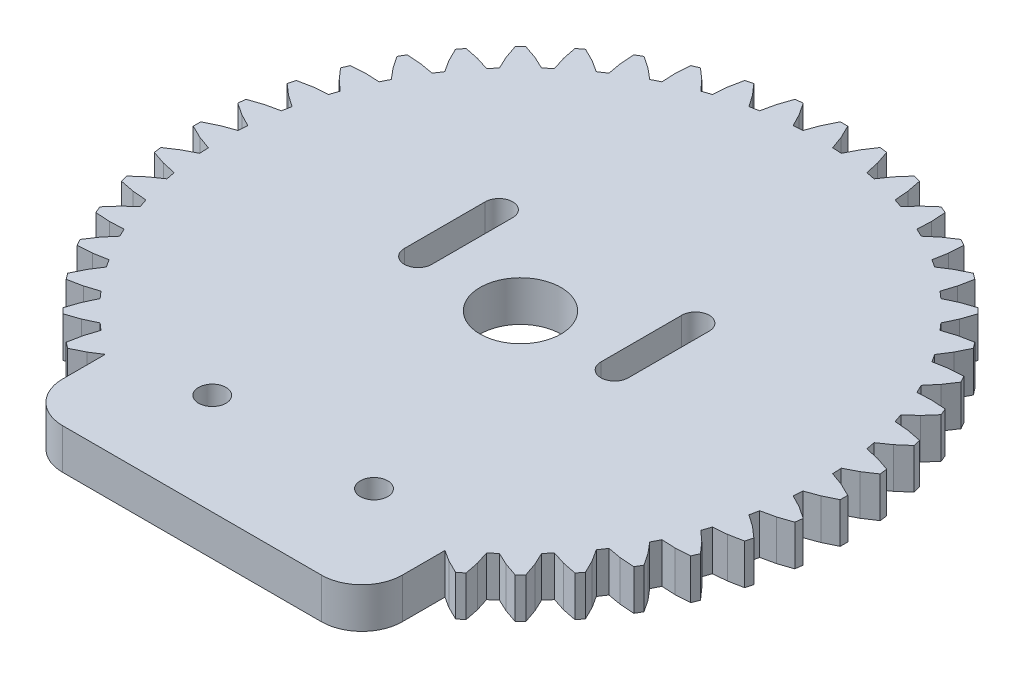
SolidWorks part; units mm, degrees
material "Acrylic (Medium-high impact)"
ref_plane "Front Plane" through (0, 0, 0) normal (0, 0, 1) x (1, 0, 0)
ref_plane "Top Plane" through (0, 0, 0) normal (0, 1, 0) x (1, 0, 0)
ref_plane "Right Plane" through (0, 0, 0) normal (1, 0, 0) x (0, 0, -1)
sketch "Sketch2" plane through (0, 0, 0) normal (0, 1, 0) x (1, 0, 0)
  line L0 (83.8835, 67.191) -> (85.5092, 66.6061)
  line L1 (85.5092, 66.6061) -> (87.1271, 65.8138)
  line L2 (87.1271, 65.8138) -> (87.1271, 64.8854)
  line L3 (87.1271, 64.8854) -> (85.5092, 64.0931)
  line L4 (85.5092, 64.0931) -> (83.8835, 63.5083)
  line L5 (83.8835, 63.5083) -> (83.8095, 62.3776)
  line L6 (83.8095, 62.3776) -> (85.3448, 61.5855)
  line L7 (85.3448, 61.5855) -> (86.8456, 60.5888)
  line L8 (86.8456, 60.5888) -> (86.7243, 59.6683)
  line L9 (86.7243, 59.6683) -> (85.0168, 59.094)
  line L10 (85.0168, 59.094) -> (83.3288, 58.7263)
  line L11 (83.3288, 58.7263) -> (83.1077, 57.615)
  line L12 (83.1077, 57.615) -> (84.5266, 56.6293)
  line L13 (84.5266, 56.6293) -> (85.8844, 55.4453)
  line L14 (85.8844, 55.4453) -> (85.6441, 54.5485)
  line L15 (85.6441, 54.5485) -> (83.8761, 54.202)
  line L16 (83.8761, 54.202) -> (82.1545, 54.0577)
  line L17 (82.1545, 54.0577) -> (81.7903, 52.9848)
  line L18 (81.7903, 52.9848) -> (83.0684, 51.8222)
  line L19 (83.0684, 51.8222) -> (84.26, 50.4711)
  line L20 (84.26, 50.4711) -> (83.9048, 49.6134)
  line L21 (83.9048, 49.6134) -> (82.1066, 49.5006)
  line L22 (82.1066, 49.5006) -> (80.3809, 49.5823)
  line L23 (80.3809, 49.5823) -> (79.8799, 48.5661)
  line L24 (79.8799, 48.5661) -> (80.9952, 47.2468)
  line L25 (80.9952, 47.2468) -> (82.0003, 45.7516)
  line L26 (82.0003, 45.7516) -> (81.5361, 44.9476)
  line L27 (81.5361, 44.9476) -> (79.7387, 45.0704)
  line L28 (79.7387, 45.0704) -> (78.0384, 45.3766)
  line L29 (78.0384, 45.3766) -> (77.4089, 44.4346)
  line L30 (77.4089, 44.4346) -> (78.3426, 42.9809)
  line L31 (78.3426, 42.9809) -> (79.1439, 41.3674)
  line L32 (79.1439, 41.3674) -> (78.5788, 40.6309)
  line L33 (78.5788, 40.6309) -> (76.8128, 40.9873)
  line L34 (76.8128, 40.9873) -> (75.167, 41.5128)
  line L35 (75.167, 41.5128) -> (74.4199, 40.6609)
  line L36 (74.4199, 40.6609) -> (75.1558, 39.0979)
  line L37 (75.1558, 39.0979) -> (75.7397, 37.3936)
  line L38 (75.7397, 37.3936) -> (75.0832, 36.737)
  line L39 (75.0832, 36.737) -> (73.3788, 37.3209)
  line L40 (73.3788, 37.3209) -> (71.8158, 38.0569)
  line L41 (71.8158, 38.0569) -> (70.9639, 37.3097)
  line L42 (70.9639, 37.3097) -> (71.4895, 35.6639)
  line L43 (71.4895, 35.6639) -> (71.8459, 33.898)
  line L44 (71.8459, 33.898) -> (71.1093, 33.3328)
  line L45 (71.1093, 33.3328) -> (69.4958, 34.1341)
  line L46 (69.4958, 34.1341) -> (68.0421, 35.0679)
  line L47 (68.0421, 35.0679) -> (67.1001, 34.4384)
  line L48 (67.1001, 34.4384) -> (67.4064, 32.738)
  line L49 (67.4064, 32.738) -> (67.5292, 30.9407)
  line L50 (67.5292, 30.9407) -> (66.7251, 30.4764)
  line L51 (66.7251, 30.4764) -> (65.23, 31.4815)
  line L52 (65.23, 31.4815) -> (63.9107, 32.5969)
  line L53 (63.9107, 32.5969) -> (62.8945, 32.0958)
  line L54 (62.8945, 32.0958) -> (62.9762, 30.3701)
  line L55 (62.9762, 30.3701) -> (62.8633, 28.572)
  line L56 (62.8633, 28.572) -> (62.0056, 28.2167)
  line L57 (62.0056, 28.2167) -> (60.6545, 29.4083)
  line L58 (60.6545, 29.4083) -> (59.4919, 30.6864)
  line L59 (59.4919, 30.6864) -> (58.419, 30.3222)
  line L60 (58.419, 30.3222) -> (58.2748, 28.6006)
  line L61 (58.2748, 28.6006) -> (57.9283, 26.8327)
  line L62 (57.9283, 26.8327) -> (57.0315, 26.5924)
  line L63 (57.0315, 26.5924) -> (55.8474, 27.9502)
  line L64 (55.8474, 27.9502) -> (54.8618, 29.369)
  line L65 (54.8618, 29.369) -> (53.7504, 29.1479)
  line L66 (53.7504, 29.1479) -> (53.3827, 27.4599)
  line L67 (53.3827, 27.4599) -> (52.8084, 25.7524)
  line L68 (52.8084, 25.7524) -> (51.888, 25.6311)
  line L69 (51.888, 25.6311) -> (50.8913, 27.1319)
  line L70 (50.8913, 27.1319) -> (50.0992, 28.6672)
  line L71 (50.0992, 28.6672) -> (48.9685, 28.5932)
  line L72 (48.9685, 28.5932) -> (48.3836, 26.9675)
  line L73 (48.3836, 26.9675) -> (47.5914, 25.3496)
  line L74 (47.5914, 25.3496) -> (46.6629, 25.3496)
  line L75 (46.6629, 25.3496) -> (45.8707, 26.9675)
  line L76 (45.8707, 26.9675) -> (45.2858, 28.5932)
  line L77 (45.2858, 28.5932) -> (44.1551, 28.6672)
  line L78 (44.1551, 28.6672) -> (43.363, 27.1319)
  line L79 (43.363, 27.1319) -> (42.3663, 25.6311)
  line L80 (42.3663, 25.6311) -> (41.4459, 25.7524)
  line L81 (41.4459, 25.7524) -> (40.8715, 27.4599)
  line L82 (40.8715, 27.4599) -> (40.5038, 29.1479)
  line L83 (40.5038, 29.1479) -> (39.3925, 29.369)
  line L84 (39.3925, 29.369) -> (38.4068, 27.9502)
  line L85 (38.4068, 27.9502) -> (37.2228, 26.5924)
  line L86 (37.2228, 26.5924) -> (36.326, 26.8327)
  line L87 (36.326, 26.8327) -> (35.9795, 28.6006)
  line L88 (35.9795, 28.6006) -> (35.8352, 30.3222)
  line L89 (35.8352, 30.3222) -> (34.7624, 30.6864)
  line L90 (34.7624, 30.6864) -> (33.5998, 29.4083)
  line L91 (33.5998, 29.4083) -> (32.2487, 28.2167)
  line L92 (32.2487, 28.2167) -> (31.3909, 28.572)
  line L93 (31.3909, 28.572) -> (31.2781, 30.3701)
  line L94 (31.2781, 30.3701) -> (31.3598, 32.0958)
  line L95 (31.3598, 32.0958) -> (30.3436, 32.5969)
  line L96 (30.3436, 32.5969) -> (29.0243, 31.4815)
  line L97 (29.0243, 31.4815) -> (27.5292, 30.4764)
  line L98 (27.5292, 30.4764) -> (26.7251, 30.9407)
  line L99 (26.7251, 30.9407) -> (26.8479, 32.738)
  line L100 (26.8479, 32.738) -> (27.1541, 34.4384)
  line L101 (27.1541, 34.4384) -> (26.2121, 35.0679)
  line L102 (26.2121, 35.0679) -> (24.7585, 34.1341)
  line L103 (24.7585, 34.1341) -> (23.1449, 33.3328)
  line L104 (23.1449, 33.3328) -> (22.4084, 33.898)
  line L105 (22.4084, 33.898) -> (22.7648, 35.6639)
  line L106 (22.7648, 35.6639) -> (23.2904, 37.3097)
  line L107 (23.2904, 37.3097) -> (22.4384, 38.0569)
  line L108 (22.4384, 38.0569) -> (20.8754, 37.3209)
  line L109 (20.8754, 37.3209) -> (19.1711, 36.737)
  line L110 (19.1711, 36.737) -> (18.5146, 37.3936)
  line L111 (18.5146, 37.3936) -> (19.0984, 39.0979)
  line L112 (19.0984, 39.0979) -> (19.8344, 40.6609)
  line L113 (19.8344, 40.6609) -> (19.0872, 41.5128)
  line L114 (19.0872, 41.5128) -> (17.4414, 40.9873)
  line L115 (17.4414, 40.9873) -> (15.6755, 40.6309)
  line L116 (15.6755, 40.6309) -> (15.1103, 41.3674)
  line L117 (15.1103, 41.3674) -> (15.9116, 42.9809)
  line L118 (15.9116, 42.9809) -> (16.8454, 44.4346)
  line L119 (16.8454, 44.4346) -> (16.2159, 45.3766)
  line L120 (16.2159, 45.3766) -> (14.5155, 45.0704)
  line L121 (14.5155, 45.0704) -> (12.7182, 44.9476)
  line L122 (12.7182, 44.9476) -> (12.2539, 45.7516)
  line L123 (12.2539, 45.7516) -> (13.2591, 47.2468)
  line L124 (13.2591, 47.2468) -> (14.3744, 48.5661)
  line L125 (14.3744, 48.5661) -> (13.8733, 49.5823)
  line L126 (13.8733, 49.5823) -> (12.1476, 49.5006)
  line L127 (12.1476, 49.5006) -> (10.3495, 49.6134)
  line L128 (10.3495, 49.6134) -> (9.9942, 50.4711)
  line L129 (9.9942, 50.4711) -> (11.1858, 51.8222)
  line L130 (11.1858, 51.8222) -> (12.4639, 52.9848)
  line L131 (12.4639, 52.9848) -> (12.0997, 54.0577)
  line L132 (12.0997, 54.0577) -> (10.3781, 54.202)
  line L133 (10.3781, 54.202) -> (8.6102, 54.5485)
  line L134 (8.6102, 54.5485) -> (8.3699, 55.4453)
  line L135 (8.3699, 55.4453) -> (9.7277, 56.6293)
  line L136 (9.7277, 56.6293) -> (11.1465, 57.615)
  line L137 (11.1465, 57.615) -> (10.9255, 58.7263)
  line L138 (10.9255, 58.7263) -> (9.2374, 59.094)
  line L139 (9.2374, 59.094) -> (7.5299, 59.6683)
  line L140 (7.5299, 59.6683) -> (7.4086, 60.5888)
  line L141 (7.4086, 60.5888) -> (8.9094, 61.5855)
  line L142 (8.9094, 61.5855) -> (10.4448, 62.3776)
  line L143 (10.4448, 62.3776) -> (10.3707, 63.5083)
  line L144 (10.3707, 63.5083) -> (8.745, 64.0931)
  line L145 (8.745, 64.0931) -> (7.1271, 64.8854)
  line L146 (7.1271, 64.8854) -> (7.1271, 65.8138)
  line L147 (7.1271, 65.8138) -> (8.745, 66.6061)
  line L148 (8.745, 66.6061) -> (10.3707, 67.191)
  line L149 (10.3707, 67.191) -> (10.4448, 68.3216)
  line L150 (10.4448, 68.3216) -> (8.9094, 69.1138)
  line L151 (8.9094, 69.1138) -> (7.4086, 70.1105)
  line L152 (7.4086, 70.1105) -> (7.5299, 71.0309)
  line L153 (7.5299, 71.0309) -> (9.2374, 71.6052)
  line L154 (9.2374, 71.6052) -> (10.9255, 71.9729)
  line L155 (10.9255, 71.9729) -> (11.1465, 73.0842)
  line L156 (11.1465, 73.0842) -> (9.7277, 74.0699)
  line L157 (9.7277, 74.0699) -> (8.3699, 75.254)
  line L158 (8.3699, 75.254) -> (8.6102, 76.1508)
  line L159 (8.6102, 76.1508) -> (10.3781, 76.4973)
  line L160 (10.3781, 76.4973) -> (12.0997, 76.6415)
  line L161 (12.0997, 76.6415) -> (12.4639, 77.7144)
  line L162 (12.4639, 77.7144) -> (11.1858, 78.877)
  line L163 (11.1858, 78.877) -> (9.9942, 80.2281)
  line L164 (9.9942, 80.2281) -> (10.3495, 81.0858)
  line L165 (10.3495, 81.0858) -> (12.1476, 81.1987)
  line L166 (12.1476, 81.1987) -> (13.8733, 81.117)
  line L167 (13.8733, 81.117) -> (14.3744, 82.1332)
  line L168 (14.3744, 82.1332) -> (13.2591, 83.4525)
  line L169 (13.2591, 83.4525) -> (12.2539, 84.9476)
  line L170 (12.2539, 84.9476) -> (12.7182, 85.7516)
  line L171 (12.7182, 85.7516) -> (14.5155, 85.6289)
  line L172 (14.5155, 85.6289) -> (16.2159, 85.3226)
  line L173 (16.2159, 85.3226) -> (16.8454, 86.2646)
  line L174 (16.8454, 86.2646) -> (15.9116, 87.7183)
  line L175 (15.9116, 87.7183) -> (15.1103, 89.3318)
  line L176 (15.1103, 89.3318) -> (15.6755, 90.0684)
  line L177 (15.6755, 90.0684) -> (17.4414, 89.712)
  line L178 (17.4414, 89.712) -> (19.0872, 89.1864)
  line L179 (19.0872, 89.1864) -> (19.8344, 90.0383)
  line L180 (19.8344, 90.0383) -> (19.0984, 91.6013)
  line L181 (19.0984, 91.6013) -> (18.5146, 93.3057)
  line L182 (18.5146, 93.3057) -> (19.1711, 93.9622)
  line L183 (19.1711, 93.9622) -> (20.8754, 93.3783)
  line L184 (20.8754, 93.3783) -> (22.4384, 92.6424)
  line L185 (22.4384, 92.6424) -> (23.2904, 93.3895)
  line L186 (23.2904, 93.3895) -> (22.7648, 95.0353)
  line L187 (22.7648, 95.0353) -> (22.4084, 96.8013)
  line L188 (22.4084, 96.8013) -> (23.1449, 97.3664)
  line L189 (23.1449, 97.3664) -> (24.7585, 96.5651)
  line L190 (24.7585, 96.5651) -> (26.2121, 95.6314)
  line L191 (26.2121, 95.6314) -> (27.1541, 96.2609)
  line L192 (27.1541, 96.2609) -> (26.8479, 97.9612)
  line L193 (26.8479, 97.9612) -> (26.7251, 99.7586)
  line L194 (26.7251, 99.7586) -> (27.5292, 100.2228)
  line L195 (27.5292, 100.2228) -> (29.0243, 99.2177)
  line L196 (29.0243, 99.2177) -> (30.3436, 98.1023)
  line L197 (30.3436, 98.1023) -> (31.3598, 98.6034)
  line L198 (31.3598, 98.6034) -> (31.2781, 100.3291)
  line L199 (31.2781, 100.3291) -> (31.3909, 102.1272)
  line L200 (31.3909, 102.1272) -> (32.2487, 102.4825)
  line L201 (32.2487, 102.4825) -> (33.5998, 101.2909)
  line L202 (33.5998, 101.2909) -> (34.7624, 100.0128)
  line L203 (34.7624, 100.0128) -> (35.8352, 100.377)
  line L204 (35.8352, 100.377) -> (35.9795, 102.0986)
  line L205 (35.9795, 102.0986) -> (36.326, 103.8666)
  line L206 (36.326, 103.8666) -> (37.2228, 104.1068)
  line L207 (37.2228, 104.1068) -> (38.4068, 102.7491)
  line L208 (38.4068, 102.7491) -> (39.3925, 101.3302)
  line L209 (39.3925, 101.3302) -> (40.5038, 101.5513)
  line L210 (40.5038, 101.5513) -> (40.8715, 103.2393)
  line L211 (40.8715, 103.2393) -> (41.4459, 104.9468)
  line L212 (41.4459, 104.9468) -> (42.3663, 105.0681)
  line L213 (42.3663, 105.0681) -> (43.363, 103.5673)
  line L214 (43.363, 103.5673) -> (44.1551, 102.032)
  line L215 (44.1551, 102.032) -> (45.2858, 102.106)
  line L216 (45.2858, 102.106) -> (45.8707, 103.7317)
  line L217 (45.8707, 103.7317) -> (46.6629, 105.3496)
  line L218 (46.6629, 105.3496) -> (47.5914, 105.3496)
  line L219 (47.5914, 105.3496) -> (48.3836, 103.7317)
  line L220 (48.3836, 103.7317) -> (48.9685, 102.106)
  line L221 (48.9685, 102.106) -> (50.0992, 102.032)
  line L222 (50.0992, 102.032) -> (50.8913, 103.5673)
  line L223 (50.8913, 103.5673) -> (51.888, 105.0681)
  line L224 (51.888, 105.0681) -> (52.8084, 104.9468)
  line L225 (52.8084, 104.9468) -> (53.3827, 103.2393)
  line L226 (53.3827, 103.2393) -> (53.7504, 101.5513)
  line L227 (53.7504, 101.5513) -> (54.8618, 101.3302)
  line L228 (54.8618, 101.3302) -> (55.8474, 102.7491)
  line L229 (55.8474, 102.7491) -> (57.0315, 104.1068)
  line L230 (57.0315, 104.1068) -> (57.9283, 103.8666)
  line L231 (57.9283, 103.8666) -> (58.2748, 102.0986)
  line L232 (58.2748, 102.0986) -> (58.419, 100.377)
  line L233 (58.419, 100.377) -> (59.4919, 100.0128)
  line L234 (59.4919, 100.0128) -> (60.6545, 101.2909)
  line L235 (60.6545, 101.2909) -> (62.0056, 102.4825)
  line L236 (62.0056, 102.4825) -> (62.8633, 102.1272)
  line L237 (62.8633, 102.1272) -> (62.9762, 100.3291)
  line L238 (62.9762, 100.3291) -> (62.8945, 98.6034)
  line L239 (62.8945, 98.6034) -> (63.9107, 98.1023)
  line L240 (63.9107, 98.1023) -> (65.23, 99.2177)
  line L241 (65.23, 99.2177) -> (66.7251, 100.2228)
  line L242 (66.7251, 100.2228) -> (67.5292, 99.7586)
  line L243 (67.5292, 99.7586) -> (67.4064, 97.9612)
  line L244 (67.4064, 97.9612) -> (67.1001, 96.2609)
  line L245 (67.1001, 96.2609) -> (68.0421, 95.6314)
  line L246 (68.0421, 95.6314) -> (69.4958, 96.5651)
  line L247 (69.4958, 96.5651) -> (71.1093, 97.3664)
  line L248 (71.1093, 97.3664) -> (71.8459, 96.8013)
  line L249 (71.8459, 96.8013) -> (71.4895, 95.0353)
  line L250 (71.4895, 95.0353) -> (70.9639, 93.3895)
  line L251 (70.9639, 93.3895) -> (71.8158, 92.6424)
  line L252 (71.8158, 92.6424) -> (73.3788, 93.3783)
  line L253 (73.3788, 93.3783) -> (75.0832, 93.9622)
  line L254 (75.0832, 93.9622) -> (75.7397, 93.3057)
  line L255 (75.7397, 93.3057) -> (75.1558, 91.6013)
  line L256 (75.1558, 91.6013) -> (74.4199, 90.0383)
  line L257 (74.4199, 90.0383) -> (75.167, 89.1864)
  line L258 (75.167, 89.1864) -> (76.8128, 89.712)
  line L259 (76.8128, 89.712) -> (78.5788, 90.0684)
  line L260 (78.5788, 90.0684) -> (79.1439, 89.3318)
  line L261 (79.1439, 89.3318) -> (78.3426, 87.7183)
  line L262 (78.3426, 87.7183) -> (77.4089, 86.2646)
  line L263 (77.4089, 86.2646) -> (78.0384, 85.3226)
  line L264 (78.0384, 85.3226) -> (79.7387, 85.6289)
  line L265 (79.7387, 85.6289) -> (81.5361, 85.7516)
  line L266 (81.5361, 85.7516) -> (82.0003, 84.9476)
  line L267 (82.0003, 84.9476) -> (80.9952, 83.4525)
  line L268 (80.9952, 83.4525) -> (79.8799, 82.1332)
  line L269 (79.8799, 82.1332) -> (80.3809, 81.117)
  line L270 (80.3809, 81.117) -> (82.1066, 81.1987)
  line L271 (82.1066, 81.1987) -> (83.9048, 81.0858)
  line L272 (83.9048, 81.0858) -> (84.26, 80.2281)
  line L273 (84.26, 80.2281) -> (83.0684, 78.877)
  line L274 (83.0684, 78.877) -> (81.7903, 77.7144)
  line L275 (81.7903, 77.7144) -> (82.1545, 76.6415)
  line L276 (82.1545, 76.6415) -> (83.8761, 76.4973)
  line L277 (83.8761, 76.4973) -> (85.6441, 76.1508)
  line L278 (85.6441, 76.1508) -> (85.8844, 75.254)
  line L279 (85.8844, 75.254) -> (84.5266, 74.0699)
  line L280 (84.5266, 74.0699) -> (83.1077, 73.0842)
  line L281 (83.1077, 73.0842) -> (83.3288, 71.9729)
  line L282 (83.3288, 71.9729) -> (85.0168, 71.6052)
  line L283 (85.0168, 71.6052) -> (86.7243, 71.0309)
  line L284 (86.7243, 71.0309) -> (86.8456, 70.1105)
  line L285 (86.8456, 70.1105) -> (85.3448, 69.1138)
  line L286 (85.3448, 69.1138) -> (83.8095, 68.3216)
  line L287 (83.8095, 68.3216) -> (83.8835, 67.191)
  line L288 (47.1271, 105.3496) -> (47.1271, 25.3496) construction
  line L289 (7.1271, 65.3496) -> (87.1271, 65.3496) construction
  circle A0 centre (47.1271, 65.3496) radius 5
  point P292 (47.1271, 65.3496)
  dimension "D1" = 10
sketch "Sketch7" plane through (0, 0, 0) normal (0, 1, 0) x (1, 0, 0)
  line L0 (47.1271, 65.3496) -> (47.1271, 5.5554) construction
  line L1 (47.1271, 105.3496) -> (47.1271, 25.3496) construction
  circle A0 centre (37.1271, 37.2366) radius 1.7
  circle A1 centre (57.1271, 37.2366) radius 1.7
  dimension "D3" = 3.4
  dimension "D1" = 20
  dimension "D2" = 28.113
sketch "Sketch8" plane through (0, 0, 0) normal (0, 1, 0) x (1, 0, 0)
  line L0 (37.1271, 37.2366) -> (57.1271, 37.2366) construction
  line L2 (26.1271, 49.7366) -> (68.1271, 49.7366)
  line L3 (26.1271, 49.7366) -> (26.1271, 24.7366)
  line L4 (26.1271, 24.7366) -> (68.1271, 24.7366)
  line L5 (68.1271, 49.7366) -> (68.1271, 24.7366)
  line L6 (26.1271, 49.7366) -> (68.1271, 24.7366) construction
  line L7 (26.1271, 24.7366) -> (68.1271, 49.7366) construction
  point P4 (47.1271, 37.2366)
  dimension "D1" = 42
  dimension "D2" = 25
extrude "Boss-Extrude3" add sketch "Sketch2" along normal blind 5
extrude "Boss-Extrude4" add sketch "Sketch8" along normal up to surface (5 mm away) up to face at (47.1271, 5, -65.3496)
extrude "Cut-Extrude1" cut sketch "Sketch7" along normal through all
sketch "Sketch10" plane through (0, 0, 0) normal (0, -1, 0) x (1, 0, 0)
  line L0 (34.9771, -64.8366) -> (34.9771, -74.8366) construction
  line L1 (36.6771, -64.8366) -> (36.6771, -74.8366)
  line L2 (33.2771, -64.8366) -> (33.2771, -74.8366)
  line L3 (59.2771, -64.8366) -> (59.2771, -74.8366) construction
  line L4 (60.9771, -64.8366) -> (60.9771, -74.8366)
  line L5 (57.5771, -64.8366) -> (57.5771, -74.8366)
  circle A0 centre (59.2771, -69.8366) radius 1.7
  circle A1 centre (34.9771, -69.8366) radius 1.7
  circle A2 centre (34.9771, -69.8366) radius 1.7 construction
  circle A3 centre (59.2771, -69.8366) radius 1.7 construction
  arc A4 (36.6771, -64.8366) -> (33.2771, -64.8366) centre (34.9771, -64.8366) ccw
  arc A5 (33.2771, -74.8366) -> (36.6771, -74.8366) centre (34.9771, -74.8366) ccw
  arc A6 (60.9771, -64.8366) -> (57.5771, -64.8366) centre (59.2771, -64.8366) ccw
  arc A7 (57.5771, -74.8366) -> (60.9771, -74.8366) centre (59.2771, -74.8366) ccw
  point P8 (34.9771, -69.8366)
  point P19 (59.2771, -69.8366)
  dimension "D1" = 10
extrude "Cut-Extrude2" cut sketch "Sketch10" against normal up to next contours L1 A4 L2 A1 | A1 | L2 A5 L1 A1 | L4 A6 L5 A0 | A0 | L5 A7 L4 A0 region at (34.9771, 0, -66.0014) region at (34.9771, 0, -69.8366) region at (34.9771, 0, -73.6718) region at (59.2771, 0, -66.0014) region at (59.2771, 0, -69.8366) region at (59.2771, 0, -73.6718)
fillet "Fillet1" radius 5 2 edges at (68.1271, 2.5, -24.7366) (26.1271, 2.5, -24.7366)
ref_axis "Axis5" through (47.1271, 5, -65.3496) along (0, -1, 0)
